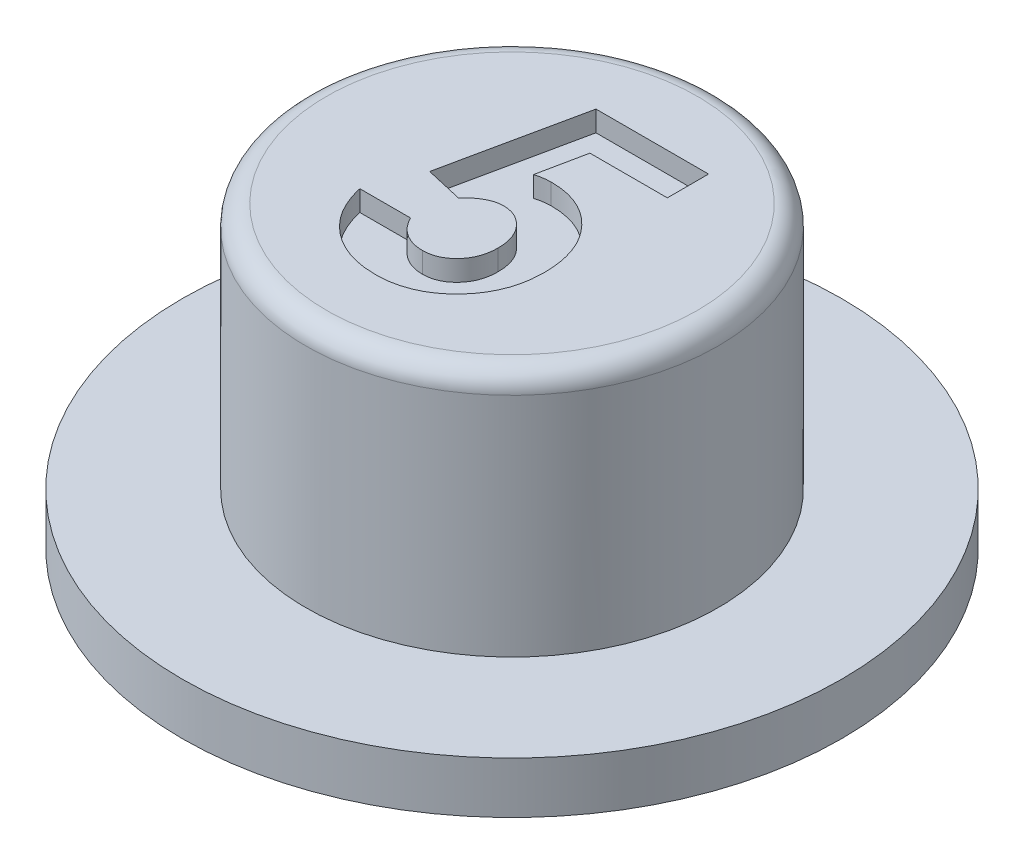
SolidWorks part; units mm, degrees
ref_plane "Front Plane" through (0, 0, 0) normal (0, 0, 1) x (1, 0, 0)
ref_plane "Top Plane" through (0, 0, 0) normal (0, 1, 0) x (1, 0, 0)
ref_plane "Right Plane" through (0, 0, 0) normal (1, 0, 0) x (0, 0, -1)
sketch "Sketch1" plane through (0, 0, 0) normal (0, 0, 1) x (1, 0, 0)
  line L1 (0, 7.25) -> (5, 7.25)
  line L2 (5, 7.25) -> (5, 1.25)
  line L3 (5, 1.25) -> (8, 1.25)
  line L4 (8, 1.25) -> (8, 0)
  line L6 (0, 7.25) -> (0, 6.9292) construction
  line L7 (0, 7.25) -> (0, 0)
  line L10 (0, 0) -> (8, 0)
  dimension "D1" = 5
  dimension "D2" = 3
  dimension "D3" = 6
  dimension "D4" = 1.25
revolve "Revolve1" add sketch "Sketch1" angle 360 about L6
sketch "Sketch2" plane through (0, 0, 0) normal (0, -1, 0) x (1, 0, 0)
  line L1 (-1.25, -1.75) -> (1.25, -1.75)
  line L2 (-1.25, -1.75) -> (-1.25, 1.75)
  line L3 (-1.25, 1.75) -> (1.25, 1.75)
  line L4 (1.25, -1.75) -> (1.25, 1.75)
  line L5 (-1.25, -1.75) -> (1.25, 1.75) construction
  line L6 (-1.25, 1.75) -> (1.25, -1.75) construction
  point P0 (0, 0)
  dimension "D1" = 2.5
  dimension "D2" = 3.5
extrude "Cut-Extrude1" cut sketch "Sketch2" against normal blind 3.5 contours L3 L4 L1 L2
fillet "Fillet1" radius 0.5 1 edges at (-5, 7.25, 0)
sketch "Sketch3" plane through (0, 7.25, 0) normal (0, 1, 0) x (1, 0, 0)
  line L0 (-3.3541, -3) -> (3.3541, -3) construction
  line L1 (0, 0) -> (0, -3) construction
  circle A0 centre (0, 0) radius 4.5 construction
  text T0 "5" font "Century Gothic" height 6
  dimension "D1" = 3
extrude "Cut-Extrude2" cut sketch "Sketch3" against normal blind 0.5
